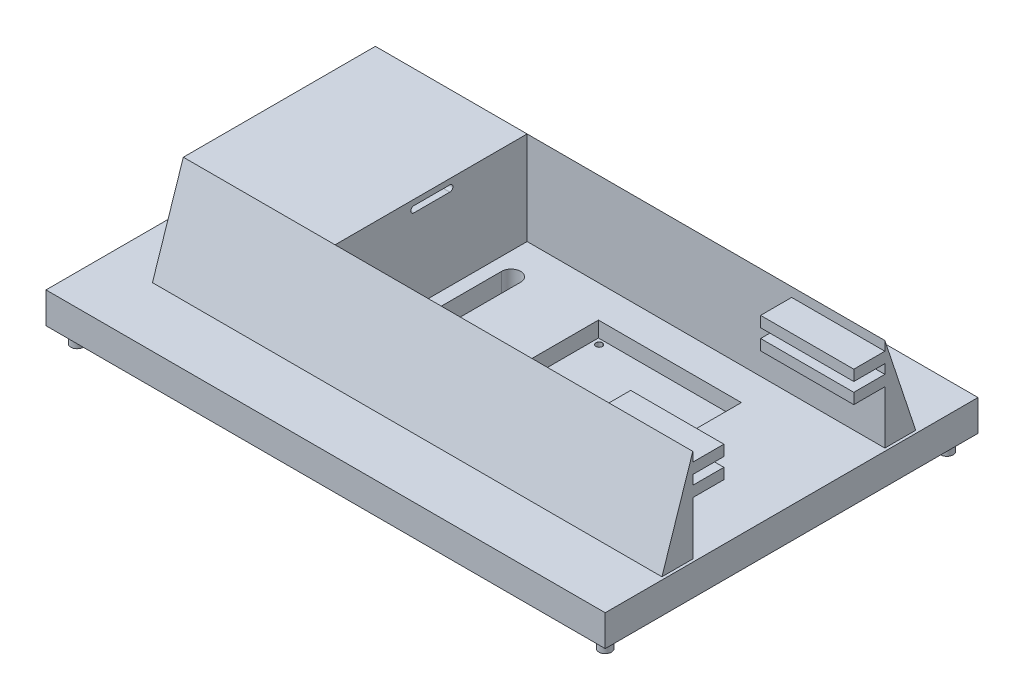
SolidWorks part; units mm, degrees
ref_plane "Front Plane" through (0, 0, 0) normal (0, 0, 1) x (1, 0, 0)
ref_plane "Top Plane" through (0, 0, 0) normal (0, 1, 0) x (1, 0, 0)
ref_plane "Right Plane" through (0, 0, 0) normal (1, 0, 0) x (0, 0, -1)
sketch "Sketch1" plane through (0, 0, 0) normal (0, 1, 0) x (1, 0, 0)
  line L1 (90, 60) -> (-90, 60)
  line L2 (90, 60) -> (90, -60)
  line L3 (90, -60) -> (-90, -60)
  line L4 (-90, 60) -> (-90, -60)
  line L5 (90, 60) -> (-90, -60) construction
  line L6 (90, -60) -> (-90, 60) construction
  point P0 (0, 0)
  dimension "D1" = 120
  dimension "D2" = 180
extrude "Boss-Extrude1" add sketch "Sketch1" along normal blind 10
sketch "Sketch2" plane through (0, 10, 0) normal (0, 1, 0) x (1, 0, 0)
  line L1 (-26.0439, 30.9093) -> (-74.8883, 30.9093)
  line L2 (-26.0439, 30.9093) -> (-26.0439, -30.9093)
  line L3 (-26.0439, -30.9093) -> (-74.8883, -30.9093)
  line L4 (-74.8883, 30.9093) -> (-74.8883, -30.9093)
  line L5 (-26.0439, 30.9093) -> (-74.8883, -30.9093) construction
  line L6 (-26.0439, -30.9093) -> (-74.8883, 30.9093) construction
  point P0 (-50.4661, 0)
extrude "Boss-Extrude2" add sketch "Sketch2" along normal blind 30
sketch "Sketch3" plane through (-74.8883, 0, 0) normal (-1, 0, 0) x (0, 0, 1)
  line L0 (30.9093, 25) -> (0, 25) construction
  line L1 (30.9093, 40) -> (30.9093, 10) construction
  line L3 (13.5, 38.5) -> (-13.5, 38.5)
  line L4 (13.5, 38.5) -> (13.5, 11.5)
  line L5 (13.5, 11.5) -> (-13.5, 11.5)
  line L6 (-13.5, 38.5) -> (-13.5, 11.5)
  line L7 (13.5, 38.5) -> (-13.5, 11.5) construction
  line L8 (13.5, 11.5) -> (-13.5, 38.5) construction
  dimension "D1" = 27
  dimension "D2" = 27
extrude "Cut-Extrude1" cut sketch "Sketch3" against normal blind 10
sketch "Sketch4" plane through (-64.8883, 0, 0) normal (-1, 0, 0) x (0, 0, 1)
  line L0 (-6.0245, 37.2243) -> (5.5495, 37.2243) construction
  line L1 (-6.0245, 38.2264) -> (5.5495, 38.2264)
  line L2 (-6.0245, 36.2222) -> (5.5495, 36.2222)
  arc A0 (-6.0245, 38.2264) -> (-6.0245, 36.2222) centre (-6.0245, 37.2243) ccw
  arc A1 (5.5495, 36.2222) -> (5.5495, 38.2264) centre (5.5495, 37.2243) ccw
  point P2 (-0.2375, 37.2243)
extrude "Cut-Extrude5" cut sketch "Sketch4" against normal through all
hole_wizard "Tap Drill for M2.5 Tap1" positions "3DSketch2" profile "Sketch8" hole size "M2.5" standard "AS"
sketch3d "3DSketch2"
  point P0 (-64.8883, 36.9534, -12.0704)
  point P2 (-64.8883, 37.0029, 11.9892)
  point P4 (-64.8883, 13.0898, 11.9186)
  point P6 (-64.8883, 13.0898, -11.8428)
sketch "Sketch8" plane through (-64.8883, 36.9534, -12.0704) normal (0, 1, 0) x (0, 0, 1)
  line L0 (0, 0) -> (0, 5.6159)
  line L1 (0, 5.6159) -> (1.025, 5)
  line L2 (1.025, 5) -> (1.025, 0.0241)
  line L3 (1.025, 0.0241) -> (1.05, 0)
  line L5 (1.05, 0) -> (0, 0)
  line L6 (-1.025, 0.0241) -> (-1.05, 0) construction
  line L10 (0, 5.6159) -> (-1.025, 5) construction
  line L11 (0, -6.35) -> (0, 107.95) construction
  dimension "Hole Dia." = 2.05
  dimension "Hole Depth" = 5
  dimension "Near C'Sink Dia." = 2.1
  dimension "Near C'Sink Angle" = 92
  dimension "Drill Angle" = 118
sketch "Sketch9" plane through (0, 10, 0) normal (0, 1, 0) x (1, 0, 0)
  line L0 (-18.7936, -19.0798) -> (-18.7936, 18.5074) construction
  line L1 (-21.8464, -19.0798) -> (-21.8464, 18.5074)
  line L2 (-15.7408, -19.0798) -> (-15.7408, 18.5074)
  arc A0 (-21.8464, -19.0798) -> (-15.7408, -19.0798) centre (-18.7936, -19.0798) ccw
  arc A1 (-15.7408, 18.5074) -> (-21.8464, 18.5074) centre (-18.7936, 18.5074) ccw
  point P2 (-18.7936, -0.2862)
extrude "Cut-Extrude6" cut sketch "Sketch9" against normal through all
sketch "Sketch10" plane through (-74.8883, 0, 0) normal (-1, 0, 0) x (0, 0, 1)
  line L0 (30.9093, 10) -> (30.9093, 40)
  line L1 (30.9093, 40) -> (40.8472, 10)
  line L2 (-60, 10) -> (60, 10) construction
  line L3 (40.8472, 10) -> (30.9093, 10)
extrude "Boss-Extrude3" add sketch "Sketch10" against normal blind 49
mirror "Mirror2" about plane through (0, 0, 0) normal (0, 0, 1) of "Boss-Extrude3"
sketch "Sketch13" plane through (-25.8883, 0, 0) normal (1, 0, 0) x (0, 0, -1)
  line L0 (-30.9093, 10) -> (-40.8472, 10)
  line L1 (-60, 10) -> (60, 10) construction
  line L2 (-30.9093, 10) -> (-40.8472, 10) construction
  line L3 (-40.8472, 10) -> (-30.9093, 40)
  line L4 (-30.9093, 40) -> (-30.9093, 10)
sketch "Sketch14" plane through (0, 10, 0) normal (0, 1, 0) x (1, 0, 0)
  line L1 (53.3281, 20.5) -> (7.3281, 20.5)
  line L2 (53.3281, 20.5) -> (53.3281, -20.5)
  line L3 (53.3281, -20.5) -> (7.3281, -20.5)
  line L4 (7.3281, 20.5) -> (7.3281, -20.5)
  line L5 (53.3281, 20.5) -> (7.3281, -20.5) construction
  line L6 (53.3281, -20.5) -> (7.3281, 20.5) construction
  point P0 (30.3281, 0)
  dimension "D1" = 46
  dimension "D2" = 41
extrude "Cut-Extrude8" cut sketch "Sketch14" against normal blind 5
hole_wizard "Tap Drill for M2.5 Tap2" positions "3DSketch3" profile "Sketch17" hole size "M2.5" standard "AS"
sketch3d "3DSketch3"
  point P0 (9.5536, 5, 18.1965)
  point P2 (9.2777, 5, -18.7664)
  point P4 (51.5506, 5, -18.3527)
  point P6 (51.5506, 5, 18.7481)
sketch "Sketch17" plane through (9.5536, 5, 18.1965) normal (1, 0, 0) x (0, 0, 1)
  line L0 (0, 0) -> (0, 5.6159)
  line L1 (0, 5.6159) -> (1.025, 5)
  line L2 (1.025, 5) -> (1.025, 0.0241)
  line L3 (1.025, 0.0241) -> (1.05, 0)
  line L5 (1.05, 0) -> (0, 0)
  line L6 (-1.025, 0.0241) -> (-1.05, 0) construction
  line L10 (0, 5.6159) -> (-1.025, 5) construction
  line L11 (0, -6.35) -> (0, 107.95) construction
  dimension "Hole Dia." = 2.05
  dimension "Hole Depth" = 5
  dimension "Near C'Sink Dia." = 2.1
  dimension "Near C'Sink Angle" = 92
  dimension "Drill Angle" = 118
sketch "Sketch18" plane through (-25.8883, 0, 0) normal (1, 0, 0) x (0, 0, -1)
  line L0 (40.8472, 10) -> (30.9093, 10)
  line L1 (30.9093, 10) -> (30.9093, 40)
  line L2 (30.9093, 40) -> (40.8472, 10)
extrude "Boss-Extrude5" add sketch "Sketch18" along normal blind 115
sketch "Sketch19" plane through (-25.8883, 0, 0) normal (1, 0, 0) x (0, 0, -1)
  line L0 (-30.9093, 10) -> (-40.8472, 10)
  line L1 (-40.8472, 10) -> (-30.9093, 40)
  line L2 (-30.9093, 40) -> (-30.9093, 10)
extrude "Boss-Extrude6" add sketch "Sketch19" along normal blind 115
sketch "Sketch25" plane through (0, 0, 0) normal (0, -1, 0) x (1, 0, 0)
  line L0 (-90, 60) -> (-90, 55)
  line L1 (-90, -60) -> (-90, 60) construction
  line L2 (-90, 55) -> (-85, 55)
  line L3 (90, 60) -> (90, 55)
  line L4 (90, 60) -> (90, -60) construction
  line L5 (90, 55) -> (85, 55)
  line L6 (90, -60) -> (90, -55)
  line L7 (90, -55) -> (85, -55)
  line L8 (-90, -60) -> (-90, -55)
  line L9 (-90, -55) -> (-85, -55)
  circle A0 centre (-85, -55) radius 2
  circle A1 centre (-85, 55) radius 2
  circle A2 centre (85, 55) radius 2
  circle A3 centre (85, -55) radius 2
  dimension "D9" = 4
  dimension "D10" = 4
  dimension "D11" = 4
  dimension "D12" = 4
  dimension "D1" = 5
  dimension "D2" = 5
  dimension "D3" = 5
  dimension "D4" = 5
  dimension "D5" = 5
  dimension "D6" = 5
  dimension "D7" = 5
  dimension "D8" = 5
extrude "Boss-Extrude9" add sketch "Sketch25" along normal blind 5 contours A1 | A0 | A2 | A3
sketch "Sketch26" plane through (0, 13.182, -39.7931) normal (0, 0.3145, -0.9493) x (-1, 0, 0)
  line L0 (-89.1117, 28.2512) -> (26.0439, 28.2512)
  dimension "D1" = 115.1557
sketch "Sketch27" plane through (-26.0439, 0, 0) normal (1, 0, 0) x (0, 0, -1)
  line L0 (0, 38.2264) -> (0, 40)
  line L1 (-5.5495, 38.2264) -> (6.0245, 38.2264) construction
  line L2 (-30.9093, 40) -> (30.9093, 40) construction
  dimension "D1" = 1.7736
sketch "Sketch29" plane through (0, 0, 30.9093) normal (0, 0, -1) x (-1, 0, 0)
  line L0 (-89.1117, 40) -> (-89.1117, 37)
  line L1 (-89.1117, 10) -> (-89.1117, 40) construction
  line L2 (-89.1117, 33.55) -> (-89.1117, 30.55)
  line L3 (-89.1117, 37) -> (-59.1117, 37)
  line L4 (-89.1117, 37) -> (-89.1117, 33.55)
  line L5 (-89.1117, 33.55) -> (-59.1117, 33.55)
  line L6 (-59.1117, 37) -> (-59.1117, 33.55)
  line L8 (-89.1117, 30.55) -> (-59.1117, 30.55)
  line L9 (-89.1117, 30.55) -> (-89.1117, 27.1)
  line L10 (-89.1117, 27.1) -> (-59.1117, 27.1)
  line L11 (-59.1117, 30.55) -> (-59.1117, 27.1)
  line M9 (-89.1117, 40) -> (-89.1117, 10)
  dimension "D1" = 3
  dimension "D2" = 30
  dimension "D3" = 3.45
  dimension "D4" = 3
  dimension "D5" = 3.45
  dimension "D6" = 30
extrude "Boss-Extrude10" add sketch "Sketch29" along normal blind 10 contours L6 L3 L5 M9 | L11 L8 L10 M9 region at (74.1117, 28.825, 30.9093) region at (74.1117, 35.275, 30.9093)
mirror "Mirror3" about plane through (0, 0, 0) normal (0, 0, 1) of "Boss-Extrude10"
